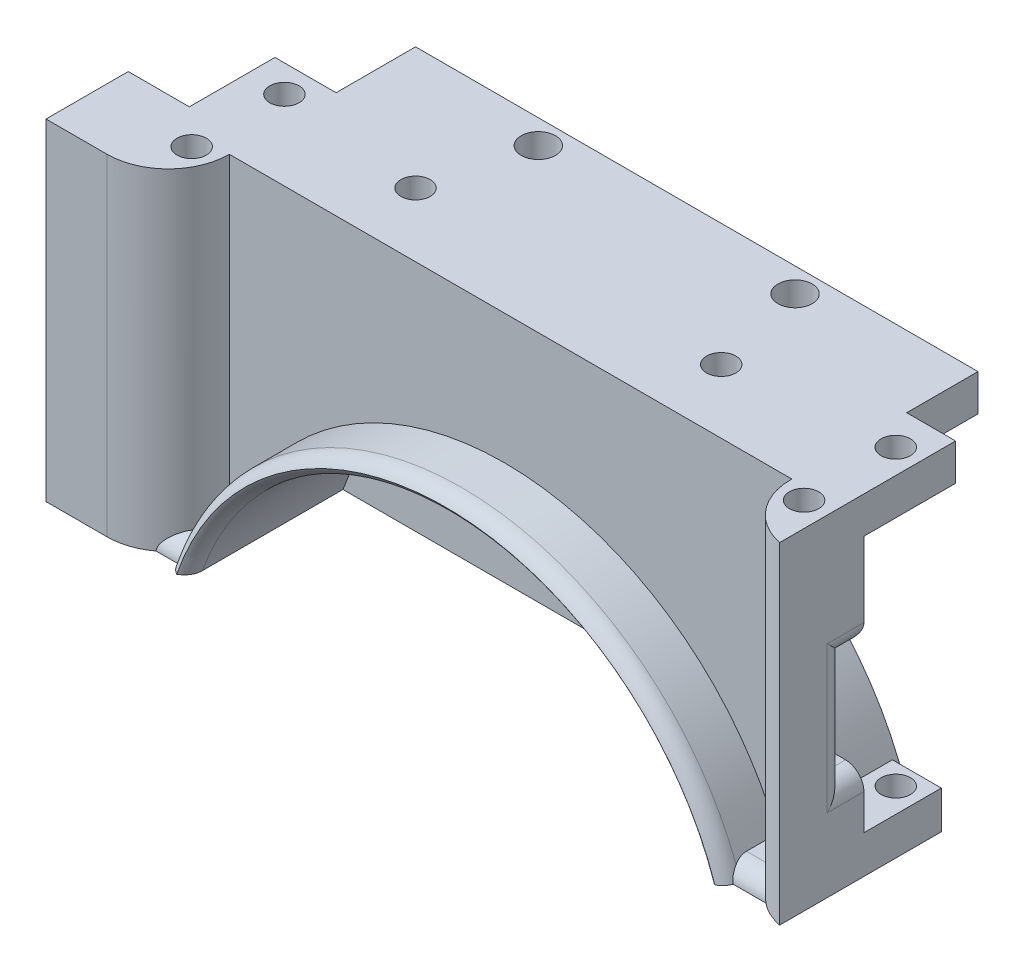
SolidWorks part; units mm, degrees
ref_plane "Front Plane" through (0, 0, 0) normal (0, 0, 1) x (1, 0, 0)
ref_plane "Top Plane" through (0, 0, 0) normal (0, 1, 0) x (1, 0, 0)
ref_plane "Right Plane" through (0, 0, 0) normal (1, 0, 0) x (0, 0, -1)
sketch "Sketch1" plane through (0, 0, 0) normal (0, 1, 0) x (1, 0, 0)
  line L0 (10, 3.275) -> (110, 3.275)
  line L1 (-10, -6.725) -> (10, -6.725)
  line L2 (-10, -6.725) -> (-10, 6.725)
  line L3 (-10, 6.725) -> (0, 6.725)
  line L4 (10, -6.725) -> (10, 3.275)
  line L5 (10, 6.725) -> (102, 6.725)
  line L6 (0, 6.725) -> (0, 20.725)
  line L7 (110, 3.275) -> (110, 6.725)
  line L8 (0, 20.725) -> (10, 20.725)
  line L9 (10, 20.725) -> (10, 6.725)
  line L10 (110, 6.725) -> (110, 19.725)
  line L11 (110, 19.725) -> (102, 19.725)
  line L12 (102, 19.725) -> (102, 6.725)
  point P0 (0, 0)
  dimension "D1" = 20
  dimension "D2" = 13.45
  dimension "D3" = 10
  dimension "D4" = 100
  dimension "D5" = 13
  dimension "D6" = 8
  dimension "D7" = 14
extrude "Boss-Extrude2" add sketch "Sketch1" along normal blind 54.2
fillet "Fillet2" radius 10 1 edges at (10, 27.1, 6.725)
sketch "Sketch2" plane through (0, 0, -3.275) normal (0, 0, 1) x (1, 0, 0)
  line L0 (10, 54.2) -> (110, 54.2) construction
  line L1 (110, 0) -> (102, 0)
  line L2 (110, 0) -> (110, 54.2)
  line L3 (110, 54.2) -> (102, 54.2)
  line L4 (102, 0) -> (102, 54.2)
  dimension "D1" = 8
extrude "Boss-Extrude3" add sketch "Sketch2" along normal blind 10
fillet "Fillet3" radius 10 1 edges at (102, 27.1, 6.725)
sketch "Sketch3" plane through (0, 0, -3.275) normal (0, 0, 1) x (1, 0, 0)
  line L1 (10, 0) -> (102, 0) construction
  line L2 (7, -15) -> (103, -15)
  line L3 (10, 54.2) -> (10, 0) construction
  arc A0 (103, -15) -> (7, -15) centre (55, -15) ccw
  dimension "D1" = 15
  dimension "D2" = 45
  dimension "D3" = 48
extrude "Boss-Extrude4" add sketch "Sketch3" along normal blind 10 and the other way blind 20
sketch "Sketch4" plane through (0, 0, 6.725) normal (0, 0, 1) x (1, 0, 0)
  line L0 (7, -15) -> (103, -15) construction
  circle A0 centre (55, -15) radius 45
  dimension "D1" = 90
extrude "Cut-Extrude1" cut sketch "Sketch4" against normal through all
sketch "Sketch5" plane through (0, 0, 6.725) normal (0, 0, 1) x (1, 0, 0)
  line L0 (9.4039, 0) -> (100.5961, 0)
  line L1 (7, -15) -> (10, -15) construction
  line L2 (10, -15) -> (105.9097, -15)
  line L3 (105.9097, -15) -> (100.5961, 0)
  arc A0 (100, -15) -> (10, -15) centre (55, -15) ccw construction
  spline S0 degree 2 poles (9.4039, 0) (-0.8331, -16.4811) (10, -15) knots 0 0 0 1 1 1
  arc M5 (10, -15) -> (100, -15) centre (55, -15) cw
extrude "Cut-Extrude2" cut sketch "Sketch5" against normal through all contours L2 L0 M5
fillet "Fillet4" radius 3 2 edges at (55, 33, 6.725) (55, 30, 6.725)
sketch "Sketch6" plane through (0, 0, -3.275) normal (0, 0, 1) x (1, 0, 0)
  line L1 (102, 0) -> (97.9701, 0)
  line L2 (102, 0) -> (102, 2.7714)
  line L3 (102, 2.7714) -> (97.9701, 2.7714)
  line L4 (97.9701, 0) -> (97.9701, 2.7714)
  arc A0 (99.0142, 0) -> (10.9858, 0) centre (55, -15) ccw construction
  dimension "D1" = 2.7714
extrude "Boss-Extrude5" add sketch "Sketch6" along normal blind 8
sketch "Sketch7" plane through (102, 0, 0) normal (1, 0, 0) x (0, 0, -1)
  line L1 (3.073, 0) -> (-4.725, 0)
  line L2 (3.073, 0) -> (3.073, 2.7714)
  line L3 (3.073, 2.7714) -> (-4.725, 2.7714)
  line L4 (-4.725, 0) -> (-4.725, 2.7714)
extrude "Boss-Extrude6" add sketch "Sketch7" along normal up to surface (3.7397 mm away)
fillet "Fillet5" radius 3 1 edges at (102.572, 2.7714, 4.725)
sketch "Sketch8" plane through (0, 0, -3.275) normal (0, 0, 1) x (1, 0, 0)
  line L1 (10.5642, 0) -> (7.2004, 0)
  line L2 (10.5642, 0) -> (10.5642, 2.77)
  line L3 (10.5642, 2.77) -> (7.2004, 2.77)
  line L4 (7.2004, 0) -> (7.2004, 2.77)
  line L5 (9.4039, 0) -> (10.9858, 0) construction
extrude "Boss-Extrude7" add sketch "Sketch8" along normal blind 8
sketch "Sketch9" plane through (7.2004, 0, 0) normal (-1, 0, 0) x (0, 0, 1)
  line L1 (3.6643, 0) -> (4.725, 0)
  line L2 (3.6643, 0) -> (3.6643, 2.77)
  line L3 (3.6643, 2.77) -> (4.725, 2.77)
  line L4 (4.725, 0) -> (4.725, 2.77)
extrude "Boss-Extrude8" add sketch "Sketch9" along normal up to surface up to face at (6.2429, 18.99, 2.8841)
fillet "Fillet12" radius 3 1 edges at (8.2821, 2.77, 4.725)
sketch "Sketch10" plane through (0, 54.2, 0) normal (0, 1, 0) x (1, 0, 0)
  line L0 (110, -6.725) -> (110, 19.725) construction
  line L1 (102, 19.725) -> (110, 19.725)
  line L2 (102, 19.725) -> (102, 13.0613)
  line L3 (102, 13.0613) -> (110, 13.0613)
  line L4 (110, 19.725) -> (110, 13.0613)
extrude "Cut-Extrude3" cut sketch "Sketch10" against normal blind 48
sketch "Sketch15" plane through (0, 0, -23.275) normal (0, 0, -1) x (-1, 0, 0)
  line L0 (-97.4264, 0) -> (-12.5736, 0)
  arc A0 (-12.5736, 0) -> (-97.4264, 0) centre (-55, -14.6489) ccw
extrude "Boss-Extrude10" add sketch "Sketch15" against normal blind 4 contours A0 L0
sketch "Sketch16" plane through (0, 0, -6.725) normal (0, 0, -1) x (-1, 0, 0)
  line L0 (-10, 54.2) -> (-10, 1.7033) construction
  line L1 (-102, 54.2) -> (-10, 54.2)
  line L2 (-102, 54.2) -> (-102, 48.2)
  line L3 (-102, 48.2) -> (-10, 48.2)
  line L4 (-10, 54.2) -> (-10, 48.2)
  dimension "D1" = 6
extrude "Boss-Extrude11" add sketch "Sketch16" along normal blind 27
sketch "Sketch17" plane through (0, 54.2, 0) normal (0, 1, 0) x (1, 0, 0)
  circle A0 centre (106, 16.275) radius 2.4
  circle A1 centre (106, 1.275) radius 2.4
  circle A2 centre (76.027, 29.775) radius 2.8
  circle A3 centre (34.027, 29.775) radius 2.8
  circle A4 centre (6, 16.275) radius 2.4
  circle A5 centre (5.83, 1.275) radius 2.4
  dimension "D1" = 4.8
  dimension "D2" = 4.8
  dimension "D3" = 4.8
  dimension "D4" = 4.8
  dimension "D5" = 5.6
  dimension "D6" = 5.6
sketch "Sketch18" plane through (0, 0, -13.0613) normal (0, 0, -1) x (-1, 0, 0)
  line L1 (-110, 54.2) -> (-102, 54.2)
  line L2 (-110, 54.2) -> (-110, 48.2)
  line L3 (-110, 48.2) -> (-102, 48.2)
  line L4 (-102, 54.2) -> (-102, 48.2)
extrude "Boss-Extrude12" add sketch "Sketch18" along normal blind 9
sketch "Sketch20" plane through (0, 0, -6.725) normal (0, 0, -1) x (-1, 0, 0)
  line L0 (-102, 43.3091) -> (-10, 43.3091) construction
  line L1 (-102, 6.2) -> (-102, 48.2) construction
  line L2 (-10, 48.2) -> (-10, 1.7033) construction
ref_plane "Plane1" through (55, 0, 0) normal (1, 0, 0) x (0, 0, -1)
sketch "Sketch26" plane through (55, 0, 0) normal (1, 0, 0) x (0, 0, -1)
  line L1 (6.8887, 51.2053) -> (6.725, 33)
  line L4 (33.725, 48.2) -> (22.0613, 48.2) construction
  line L5 (23.2583, 48.2) -> (6.8887, 51.2053)
  line L6 (6.725, 33) -> (23.2583, 48.2)
extrude "Boss-Extrude15" add sketch "Sketch26" along normal blind 47 and the other way blind 45 separate body
extrude "Cut-Extrude6" cut sketch "Sketch17" against normal through all
sketch "Sketch28" plane through (0, 54.2, 0) normal (0, 1, 0) x (1, 0, 0)
  line L0 (0, 13.725) -> (110, 13.725) construction
  line L1 (0, 20.725) -> (0, 6.725) construction
  line L2 (110, -6.725) -> (110, 22.0613) construction
  circle A0 centre (30, 13.725) radius 2.4
  circle A1 centre (80, 13.725) radius 2.4
  dimension "D1" = 4.8
  dimension "D2" = 4.8
  dimension "D3" = 50
  dimension "D4" = 30
extrude "Cut-Extrude7" cut sketch "Sketch28" against normal blind 9
sketch "Sketch29" plane through (0, 0, -6.725) normal (0, 0, -1) x (-1, 0, 0)
  line L0 (-9.4039, 0) -> (-100.5961, 0) construction
  line L1 (-103.2355, 2.7375) -> (-98.8805, 2.7375)
  line L2 (-103.2355, 2.7375) -> (-103.2355, 0)
  line L3 (-103.2355, 0) -> (-98.8805, 0)
  line L4 (-98.8805, 2.7375) -> (-98.8805, 0)
  line L5 (-110, 0) -> (-102, 0) construction
extrude "Boss-Extrude16" add sketch "Sketch29" along normal blind 12
sketch "Sketch30" plane through (0, 0, -13.0613) normal (0, 0, -1) x (-1, 0, 0)
  line L1 (-110, 48.2) -> (-102, 48.2)
  line L2 (-110, 48.2) -> (-110, 6.2)
  line L3 (-110, 6.2) -> (-102, 6.2)
  line L4 (-102, 48.2) -> (-102, 6.2)
extrude "Cut-Extrude9" cut sketch "Sketch30" against normal blind 6
sketch "Sketch31" plane through (0, 0, -7.0613) normal (0, 0, -1) x (-1, 0, 0)
  line L3 (-110.1013, 24) -> (-102, 24)
  line L5 (-102, 48.2) -> (-102, 2.7375) construction
  line L6 (-110, 0) -> (-102, 0) construction
  line L7 (-102, 6.2) -> (-102, 48.2) construction
  line L8 (-110.1013, 15.0261) -> (-102, 15.0261)
  line L9 (-110.1013, 15.0261) -> (-110.1013, 32.9739)
  line L10 (-110.1013, 32.9739) -> (-102, 32.9739)
  line L11 (-102, 15.0261) -> (-102, 32.9739)
  line L12 (-110.1013, 15.0261) -> (-102, 32.9739) construction
  line L13 (-110.1013, 32.9739) -> (-102, 15.0261) construction
  point P0 (-106.0506, 24)
  line M2 (-110, 48.2) -> (-110, 6.2)
  line M4 (-102, 6.2) -> (-102, 48.2)
  dimension "D1" = 24
extrude "Cut-Extrude16" cut sketch "Sketch31" against normal blind 3 contours L10 L3 M2 M4 | L8 L3 M2 M4
fillet "Fillet14" radius 3 5 edges at (102, 24, -4.0613) (110, 24, -4.0613) (110, 15.0261, -5.5613) (106, 32.9739, -7.0613) (110, 32.9739, -5.5613)
sketch "Sketch32" plane through (0, 0, -20.725) normal (0, 0, -1) x (-1, 0, 0)
  line L0 (-10, 48.2) -> (-10, 1.7033) construction
  line L1 (-10, 45.6058) -> (0, 45.6058)
  line L2 (-10, 45.6058) -> (-10, 5.6677)
  line L3 (-10, 5.6677) -> (0, 5.6677)
  line L4 (0, 45.6058) -> (0, 5.6677)
  line L5 (0, 54.2) -> (0, 0) construction
extrude "Cut-Extrude17" cut sketch "Sketch32" against normal blind 10
